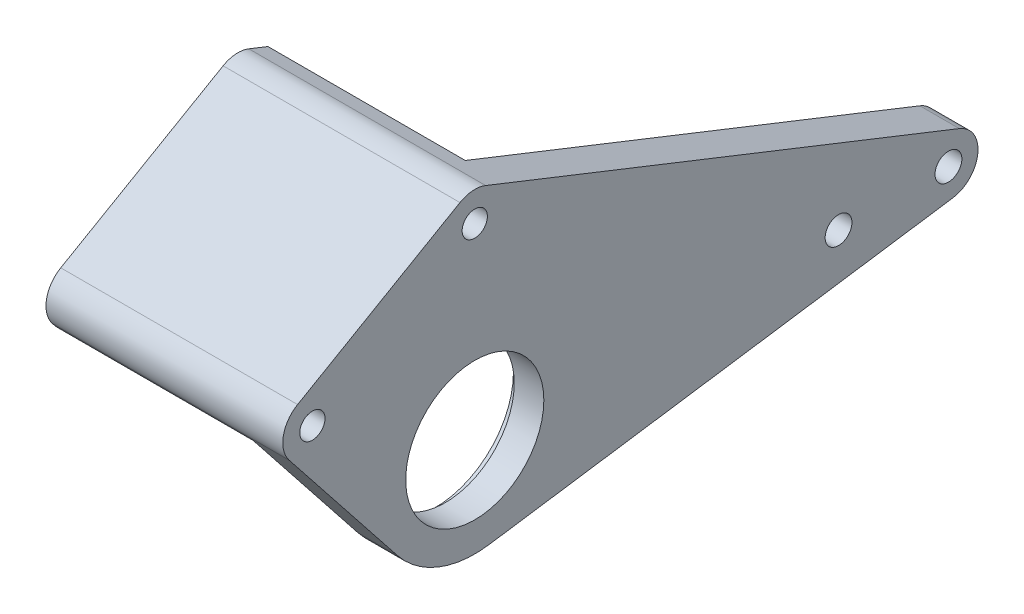
SolidWorks part; units mm, degrees
ref_plane "Front Plane" through (0, 0, 0) normal (0, 0, 1) x (1, 0, 0)
ref_plane "Top Plane" through (0, 0, 0) normal (0, 1, 0) x (1, 0, 0)
ref_plane "Right Plane" through (0, 0, 0) normal (1, 0, 0) x (0, 0, -1)
sketch "Sketch1" plane through (0, 0, 0) normal (1, 0, 0) x (0, 0, -1)
  line L0 (1.7528, 4.4282) -> (-74.4472, 34.5907)
  line L1 (-78.5812, 34.2869) -> (-104.7027, 19.2057)
  line L2 (-106.0548, 12.1242) -> (-88.6443, -9.8568)
  line L3 (-73.8849, -15.7053) -> (0.6945, -4.7116)
  line L4 (-102.3215, 15.0813) -> (-76.2, 0) construction
  line L5 (-76.2, 0) -> (-76.2, 30.1625) construction
  line L6 (0, 0) -> (-76.2, 0) construction
  circle A0 centre (0, 0) radius 2.159
  arc A1 (0.6945, -4.7116) -> (1.7528, 4.4282) centre (0, 0) ccw
  arc A2 (-74.4472, 34.5907) -> (-78.5812, 34.2869) centre (-76.2, 30.1625) ccw
  arc A3 (-104.7027, 19.2057) -> (-106.0548, 12.1242) centre (-102.3215, 15.0813) ccw
  arc A4 (-88.6443, -9.8568) -> (-73.8849, -15.7053) centre (-76.2, 0) ccw
  circle A5 centre (-76.2, 0) radius 11.1125
  circle A6 centre (-76.2, 30.1625) radius 2.032
  circle A7 centre (-76.2, 0) radius 26.1938 construction
  circle A8 centre (-102.3215, 15.0813) radius 2.032
  circle A9 centre (-17.677, 0) radius 2.159
  dimension "D1" = 4.318
  dimension "D2" = 9.525
  dimension "D3" = 22.225
  dimension "D4" = 4.7625
  dimension "D5" = 15.875
  dimension "D6" = 52.3875
  dimension "D10" = 4.064
  dimension "D7" = 30.1625
  dimension "D8" = 76.2
  dimension "D9" = 60
  dimension "D11" = 17.677
extrude "Boss-Extrude1" add sketch "Sketch1" along normal blind 6.35
sketch "Sketch2" plane through (6.35, 0, 0) normal (1, 0, 0) x (0, 0, -1)
  circle A0 centre (-76.2, 0) radius 12.573
  dimension "D1" = 25.146
extrude "Cut-Extrude1" cut sketch "Sketch2" against normal blind 1.5875
sketch "Sketch3" plane through (6.35, 0, 0) normal (1, 0, 0) x (0, 0, -1)
  line L0 (-74.4472, 34.5907) -> (-71.374, 33.3742)
  line L1 (-76.2, 33.902) -> (-79.4385, 32.0322)
  line L2 (-79.4385, 32.0322) -> (-79.4385, 28.2928)
  line L3 (-79.4385, 28.2928) -> (-76.2, 26.423)
  line L4 (-76.2, 26.423) -> (-72.9615, 28.2928)
  line L5 (-72.9615, 28.2928) -> (-72.9615, 32.0322)
  line L6 (-72.9615, 32.0322) -> (-76.2, 33.902)
  line L7 (-102.3215, 18.8207) -> (-105.56, 16.951)
  line L8 (-105.56, 16.951) -> (-105.56, 13.2115)
  line L9 (-105.56, 13.2115) -> (-102.3215, 11.3418)
  line L10 (-102.3215, 11.3418) -> (-99.083, 13.2115)
  line L11 (-99.083, 13.2115) -> (-99.083, 16.951)
  line L12 (-99.083, 16.951) -> (-102.3215, 18.8207)
  line L13 (-78.5813, 34.2869) -> (-104.7027, 19.2057)
  line L14 (-106.0548, 12.1242) -> (-102.1951, 7.2513)
  line L17 (1.7528, 4.4282) -> (-74.4472, 34.5907) construction
  line L18 (-71.374, 26.5525) -> (-71.374, 33.3742)
  line L20 (-78.5812, 34.2869) -> (-104.7027, 19.2057) construction
  line L21 (-106.0548, 12.1242) -> (-88.6443, -9.8568) construction
  circle A0 centre (-76.2, 30.1625) radius 3.2385 construction
  circle A1 centre (-102.3215, 15.0813) radius 3.2385 construction
  arc A4 (-74.4472, 34.5907) -> (-78.5813, 34.2869) centre (-76.2, 30.1625) ccw
  arc A5 (-104.7027, 19.2057) -> (-106.0548, 12.1242) centre (-102.3215, 15.0813) ccw
  arc A6 (-102.1951, 7.2513) -> (-71.374, 26.5525) centre (-76.2, 0) cw
  arc A7 (-74.4472, 34.5907) -> (-78.5812, 34.2869) centre (-76.2, 30.1625) ccw construction
  arc A8 (-104.7027, 19.2057) -> (-106.0548, 12.1242) centre (-102.3215, 15.0813) ccw construction
  line M18 (1.7528, 4.4282) -> (-74.4472, 34.5907)
  arc M19 (-74.4472, 34.5907) -> (-78.5812, 34.2869) centre (-76.2, 30.1625) ccw
  line M20 (-78.5812, 34.2869) -> (-104.7027, 19.2057)
  arc M21 (-104.7027, 19.2057) -> (-106.0548, 12.1242) centre (-102.3215, 15.0813) ccw
  line M22 (-106.0548, 12.1242) -> (-88.6443, -9.8568)
  dimension "D4" = 26.9875
  dimension "D1" = 6.477
  dimension "D2" = 6.477
  dimension "D3" = 1.5875
extrude "Boss-Extrude2" add sketch "Sketch3" along normal blind 31.75 contours A6 L10 L9 L8 L7 L12 L11 L3 L2 L1 L6 L5 L4 L18 M22 M18 M19 M20 M21 region at (6.35, 23.916, 90.2574)
fillet "Fillet1" radius 3.175 2 edges at (22.225, 26.5525, 71.374) (22.225, 7.2513, 102.1951)
mirror "Mirror1" about plane through (6.35, 0, 0) normal (1, 0, 0) of bodies 104 102
delete or keep bodies "Body-Delete/Keep 1" type delete bodies bodies 104
